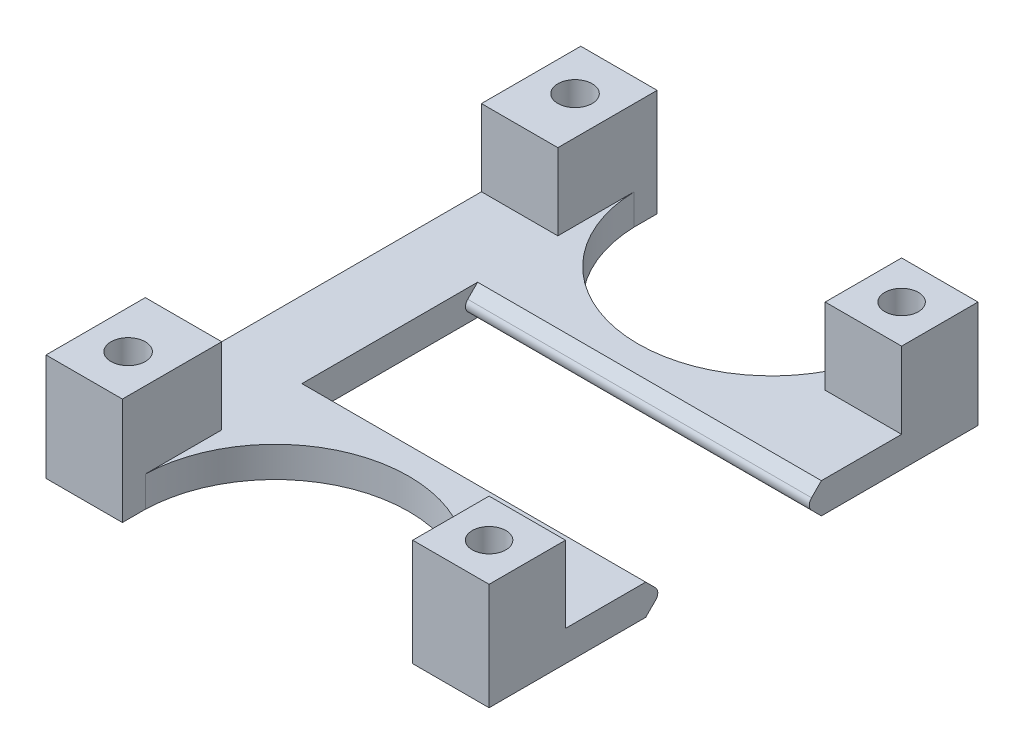
SolidWorks part; units mm, degrees
ref_plane "Front Plane" through (0, 0, 0) normal (0, 0, 1) x (1, 0, 0)
ref_plane "Top Plane" through (0, 0, 0) normal (0, 1, 0) x (1, 0, 0)
ref_plane "Right Plane" through (0, 0, 0) normal (1, 0, 0) x (0, 0, -1)
sketch "Sketch1" plane through (0, 0, 0) normal (0, 1, 0) x (1, 0, 0)
  line L0 (10, 10) -> (10, -10)
  line L2 (0, -20) -> (0, 20)
  line L4 (55, -20) -> (55, 20) construction
  line L5 (10, -10) -> (45, -10)
  line L6 (45, -10) -> (45, 10) construction
  line L7 (45, 10) -> (10, 10)
  line L8 (45, 10) -> (55, 10)
  line L11 (55, 10) -> (55, 20)
  line L13 (27.5, -20) -> (27.5, -10) construction
  line L14 (27.5, 10) -> (27.5, 20) construction
  line L16 (45, -10) -> (55, -10)
  line L17 (55, -20) -> (55, -10)
  line L18 (55, -20) -> (55, -32)
  line L19 (55, -32) -> (45, -32)
  line L20 (0, -32) -> (0, -35)
  line L21 (55, 20) -> (55, 32)
  line L22 (55, 32) -> (45, 32)
  line L23 (0, -35) -> (10, -35)
  line L24 (0, -20) -> (0, -32)
  line L26 (10, -35) -> (10, -32)
  line L27 (0, 20) -> (0, 32)
  line L29 (10, 32) -> (10, 35)
  line L30 (-55, 0) -> (55, 0) construction
  line L31 (0, 0) -> (55, 0) construction
  line L35 (10, 35) -> (0, 35)
  line L36 (0, 35) -> (0, 32)
  arc A26 (45, -32) -> (10, -32) centre (27.5, -32.5074) ccw
  arc A27 (45, 32) -> (10, 32) centre (27.5, 32.5074) cw
  circle A46 centre (50, 27) radius 2.2
  circle A47 centre (50, -27) radius 2.2
  circle A50 centre (5, 29.25) radius 2.2479
  circle A52 centre (5, -29.25) radius 2.2479
  point P30 (27.5, -15)
  point P35 (27.5, 15)
  point P36 (27.5, -10)
  point P39 (0, 0)
  dimension "D18" = 4.4
  dimension "D1" = 40
  dimension "D2" = 55
  dimension "D24" = 10
  dimension "D13" = 5
  dimension "D16" = 5
  dimension "D7" = 10
  dimension "D9" = 5
  dimension "D14" = 5
  dimension "D4" = 20
  dimension "D5" = 10
  dimension "D3" = 10
  dimension "D6" = 35
  dimension "D8" = 12
  dimension "D10" = 10
extrude "Extrude-Body" add sketch "Sketch1" along normal blind 4 contours L4 L2 A47 A46 L7 L6 L5 L0 | L19 L18 A47 | L22 L21 A46 | L27 | L24 region at (9.1098, 0, 0)
sketch "Sketch5" plane through (0, 4, 0) normal (0, 1, 0) x (1, 0, 0)
  line L9 (45, -22) -> (55, -22)
  line L21 (55, -22) -> (55, -32)
  line L23 (0, -35) -> (0, 35) construction
  line L36 (55, -32) -> (45, -32)
  line L37 (45, -32) -> (45, -22)
  line L38 (55, 22) -> (55, 32)
  line L39 (55, 32) -> (45, 32)
  line L41 (45, 32) -> (45, 22)
  line L42 (45, 22) -> (55, 22)
  line L43 (10, 22) -> (10, 35)
  line L45 (10, 35) -> (0, 35)
  line L46 (0, 35) -> (0, 22)
  line L47 (0, -35) -> (0, 35) construction
  line L48 (0, 22) -> (10, 22)
  line L49 (10, -22) -> (0, -22)
  line L50 (0, -22) -> (0, -35)
  line L52 (10, -35) -> (10, -22)
  line L55 (10, -35) -> (0, -35)
  circle A0 centre (50, 27) radius 2.2
  circle A3 centre (50, -27) radius 2.2
  circle A11 centre (50, 27) radius 2.2 construction
  circle A12 centre (50, -27) radius 2.2 construction
  circle A13 centre (5, -29.25) radius 2.2479 construction
  circle A14 centre (5, -29.25) radius 2.2479
  circle A15 centre (5, 29.25) radius 2.2479 construction
  circle A16 centre (5, 29.25) radius 2.2479
  dimension "D1" = 10
  dimension "D2" = 10
  dimension "D3" = 10
  dimension "D4" = 10
  dimension "D5" = 10
  dimension "D6" = 10
  dimension "D8" = 13
extrude "Extrude-Legs" add sketch "Sketch5" along normal blind 10
sketch "Sketch6" plane through (0, 4, 0) normal (0, 1, 0) x (1, 0, 0)
  line L0 (55, -10) -> (55, -22) construction
  line L1 (10, -10) -> (55, -10)
  line L2 (10, -10) -> (10, -9.5)
  line L3 (10, -9.5) -> (55, -9.5)
  line L4 (55, -10) -> (55, -9.5)
  line L5 (10, 10) -> (55, 10)
  line L6 (10, 10) -> (10, 9.5)
  line L7 (10, 9.5) -> (55, 9.5)
  line L8 (55, 10) -> (55, 9.5)
  line L9 (55, 10) -> (55, 22) construction
  dimension "D1" = 19
extrude "Boss-Extrude1" add sketch "Sketch6" against normal up to surface (4 mm away) up to face at (5, 0, 31.4979)
sketch "Sketch7" plane through (55, 0, 0) normal (1, 0, 0) x (0, 0, -1)
  line L0 (-10.2071, 2.7071) -> (-11.5, 4)
  line L1 (-9.5, 0) -> (-9.5, 4) construction
  line L2 (-9.5, 4) -> (-22, 4) construction
  line L3 (-10.2071, 1.2929) -> (-11.5, 0)
  line L4 (-9.5, 0) -> (-32, 0) construction
  line L5 (10.2071, 2.7071) -> (11.5, 4)
  line L6 (9.5, 0) -> (9.5, 4) construction
  line L7 (9.5, 4) -> (22, 4) construction
  line L8 (10.2071, 1.2929) -> (11.5, 0)
  line L9 (9.5, 0) -> (32, 0) construction
  line L10 (11.5, 4) -> (9.5, 4)
  line L11 (9.5, 0) -> (9.5, 4) construction
  line L12 (9.5, 4) -> (9.5, 0)
  line L13 (9.5, 0) -> (11.5, 0)
  line L14 (-11.5, 4) -> (-9.5, 4)
  line L15 (-9.5, 4) -> (-9.5, 0)
  line L16 (-9.5, 0) -> (-11.5, 0)
  line L17 (0, 0) -> (0, 8.2974) construction
  arc A0 (10.2071, 2.7071) -> (10.2071, 1.2929) centre (10.9142, 2) ccw
  arc A1 (-10.2071, 2.7071) -> (-10.2071, 1.2929) centre (-10.9142, 2) cw
  point P36 (9.5, 2)
  point P39 (-9.5, 2)
  dimension "D3" = 1
  dimension "D1" = 45
  dimension "D2" = 45
extrude "Cut-Extrude1" cut sketch "Sketch7" against normal up to surface (45 mm away) up to face at (10, 2, 0)
equation "\"boltdiameter\"=4.4"
equation "\"D18@Sketch1\"=\"boltdiameter\""
equation "\"boltfacediameter\"=7"
equation "\"insetNutFlat\"=8.4"
equation "\"screwInset\"=8.43"
equation "\"slotLength\"=80"
